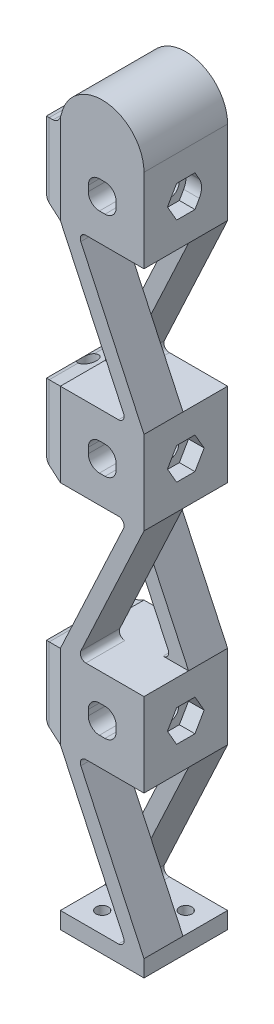
SolidWorks part; units mm, degrees
note: The reader was unsure of these and kept them because the rebuilt part matched: shared geometry of "Sketch1<3>", "Sketch1<4>", "Sketch1<5>".
material "PET"
ref_plane "Front Plane" through (0, 0, 0) normal (0, 0, 1) x (1, 0, 0)
ref_plane "Top Plane" through (0, 0, 0) normal (0, 1, 0) x (1, 0, 0)
ref_plane "Right Plane" through (0, 0, 0) normal (1, 0, 0) x (0, 0, -1)
sketch "Sketch1" plane through (0, 0, 0) normal (0, 0, 1) x (1, 0, 0)
  line L0 (0, 0) -> (57.9688, 0) construction
  line L1 (7.5, 12.867) -> (-7.5, 12.867)
  line L2 (7.5, -27.867) -> (-7.5, -27.867)
  line L3 (7.5, -27.867) -> (7.5, -12.867)
  line L4 (7.5, -12.867) -> (-7.5, -12.867)
  line L5 (-7.5, -27.867) -> (-7.5, -12.867)
  line L6 (7.5, -27.867) -> (-7.5, -12.867) construction
  line L7 (7.5, -12.867) -> (-7.5, -27.867) construction
  line L8 (-7.5, 27.867) -> (-7.5, 12.867)
  line L9 (0, 0) -> (0, 41.5625) construction
  line L10 (7.5, 27.867) -> (-7.5, 27.867)
  line L11 (7.5, 27.867) -> (7.5, 12.867)
  line L12 (-7.5, 12.867) -> (4.5, -12.867)
  line L13 (4.5, -12.867) -> (7.5, -12.867)
  line L14 (7.5, -12.867) -> (-4.5, 12.867)
  line L15 (-4.5, 12.867) -> (-7.5, 12.867)
  line L16 (7.5, 12.867) -> (-4.5, -12.867)
  line L17 (-7.5, -12.867) -> (4.5, 12.867)
  point P1 (0, -20.367)
  dimension "D1" = 15
  dimension "D2" = 65
  dimension "D3" = 3
extrude "Boss-Extrude1" add sketch "Sketch1" along normal mid plane 15 contours L5 L2 L3 L4
extrude "cross_flexure" add sketch "Sketch1<3>" against normal blind 7 from surface at 7.5 contours L17 L4 L16 L12 | L17 L14 L16 L1 | L17 L12 L16 L14 starting at face at (0, -20.367, 7.5)
sketch "Sketch1<3>" plane through (0, 0, 0) normal (0, 0, 1) x (1, 0, 0) same geometry as "Sketch1"
extrude "Boss-Extrude3" add sketch "Sketch1<4>" along normal blind 7 from surface at -7.5 contours L12 L17 L14 L1 | L14 L16 L12 L4 | L17 L12 L16 L14 starting at face at (0, -20.367, -7.5)
sketch "Sketch1<4>" plane through (0, 0, 0) normal (0, 0, 1) x (1, 0, 0) same geometry as "Sketch1"
extrude "Boss-Extrude4" add sketch "Sketch1<5>" along normal mid plane 15 contours L11 L10 L8 L1
sketch "Sketch1<5>" plane through (0, 0, 0) normal (0, 0, 1) x (1, 0, 0) same geometry as "Sketch1"
ref_plane "Plane1" through (0, 20.367, 0) normal (0, -1, 0) x (-1, 0, 0)
ref_plane "Plane2" through (7.5, -27.867, 7.5) normal (-1, 0, 0) x (0, 0, 1)
ref_plane "Plane3" through (0, -20.367, 0) normal (0, 1, 0) x (1, 0, 0)
mirror "Mirror2" about plane through (0, 20.367, 0) normal (0, -1, 0) of "cross_flexure", "Boss-Extrude3"
mirror "Mirror3" about plane through (0, 20.367, 0) normal (0, -1, 0) of "Boss-Extrude1"
mirror "Mirror4" about plane through (0, -20.367, 0) normal (0, 1, 0) of "cross_flexure"
mirror "Mirror5" about plane through (0, -20.367, 0) normal (0, 1, 0) of "Boss-Extrude3"
mirror "Mirror6" about plane through (0, -20.367, 0) normal (0, 1, 0) of "Boss-Extrude4"
sketch "Sketch29" plane through (0, 0, 7.5) normal (0, 0, 1) x (1, 0, 0)
  line L0 (7.5, 68.6011) -> (-7.5, 68.6011) construction
  line L1 (7.5, 68.6011) -> (-7.5, 68.6011)
  arc A0 (-7.5, 68.6011) -> (7.5, 68.6011) centre (0, 68.6011) cw
  line M10 (7.5, 68.6011) -> (-7.5, 68.6011)
extrude "Boss-Extrude5" add sketch "Sketch29" against normal up to surface (15 mm away) contours A0 M10 up to face at (0, 0, -7.5)
ref_plane "Plane4" through (0, -56.6011, 0) normal (0, 1, 0) x (1, 0, 0)
sketch "Sketch36" plane through (0, -56.6011, 0) normal (0, 1, 0) x (1, 0, 0)
  line L4 (7.5, -7.5) -> (7.5, 7.5)
  line L5 (7.5, 7.5) -> (-7.5, 7.5)
  line L6 (-7.5, 7.5) -> (-7.5, -7.5)
  line L7 (-7.5, -7.5) -> (7.5, -7.5)
  line L8 (7.5, -7.5) -> (7.5, 7.5)
  line L9 (7.5, 7.5) -> (-7.5, 7.5)
  line L10 (-7.5, 7.5) -> (-7.5, -7.5)
  line L11 (-7.5, -7.5) -> (7.5, -7.5)
  dimension "D1" = 0
extrude "Cut-Extrude1" cut sketch "Sketch36" against normal through all
fillet "Fillet1" radius 1 12 edges at (-4.5, -27.867, 4) (4.5, -53.6011, 4) (4.5, -27.867, -4) (-4.5, -53.6011, -4) (4.5, 12.867, 4) (-4.5, -12.867, 4) (4.5, -12.867, -4) (-4.5, 12.867, -4) (-4.5, 53.6011, 4) (4.5, 27.867, 4) (4.5, 53.6011, -4) (-4.5, 27.867, -4)
sketch "Sketch48" plane through (0, -53.6011, 0) normal (0, 1, 0) x (1, 0, 0)
  line L0 (0, 0) -> (-7.5, -7.5) construction
  line L1 (-7.5, -7.5) -> (7.5, -7.5) construction
  line L2 (0, 0) -> (-7.5, 7.5) construction
  line L3 (7.5, 7.5) -> (-7.5, 7.5) construction
  circle A0 centre (-3.75, -3.75) radius 1
  circle A1 centre (3.75, 3.75) radius 1
  point P6 (-3.75, -3.75)
  point P9 (3.75, 3.75)
  dimension "D1" = 2
hole_wizard "Ø2.2 (2.2) Diameter Hole1" positions "Sketch48" profile "Sketch49" hole size "Ø2.2" standard "DIN"
sketch "Sketch49" plane through (3.75, -53.6011, -3.75) normal (1, 0, 0) x (0, 0, 1)
  line L0 (0, 0) -> (0, 3)
  line L1 (0, 3) -> (1.1, 3)
  line L2 (1.1, 3) -> (1.1, 0)
  line L5 (1.1, 0) -> (0, 0)
  line L11 (0, -6.35) -> (0, 107.95) construction
  dimension "Thru Hole Dia." = 2.2
  dimension "Thru Hole Depth" = 3
ref_plane "Plane5" through (0, 0, 0) normal (0, 0, 1) x (1, 0, 0)
ref_plane "finger_surface" through (-12.5, 0, 0) normal (-1, 0, 0) x (0, 0, 1)
sketch "Sketch82" plane through (-12.5, 0, 0) normal (-1, 0, 0) x (0, 0, 1)
  line L0 (-6, 67.1011) -> (-6, 55.1011)
  line L1 (-6, 55.1011) -> (0.5, 55.1011)
  line L2 (0.5, 55.1011) -> (6, 55.1011)
  line L3 (6, 55.1011) -> (6, 67.1011)
  line L4 (6, 67.1011) -> (-6, 67.1011)
  line L5 (-7.5, 68.6011) -> (-7.5, 53.6011)
  line L6 (-7.5, 53.6011) -> (0.5, 53.6011)
  line L7 (0.5, 53.6011) -> (7.5, 53.6011)
  line L8 (7.5, 53.6011) -> (7.5, 68.6011)
  line L9 (7.5, 68.6011) -> (-7.5, 68.6011)
  line L10 (-7.5, 68.6011) -> (-7.5, 53.6011)
  line L11 (-7.5, 53.6011) -> (0.5, 53.6011)
  line L12 (0.5, 53.6011) -> (7.5, 53.6011)
  line L13 (7.5, 53.6011) -> (7.5, 68.6011)
  line L14 (7.5, 68.6011) -> (-7.5, 68.6011)
  dimension "D2" = 1.5
loft "Loft1" add section face at (-7.5, 59.6011, 0.1) section "Sketch82"
sketch "Sketch83" plane through (-12.5, 0, 0) normal (-1, 0, 0) x (0, 0, 1)
  line L0 (-6, 26.367) -> (-6, 14.367)
  line L1 (-6, 14.367) -> (-0.5, 14.367)
  line L2 (-0.5, 14.367) -> (6, 14.367)
  line L3 (6, 14.367) -> (6, 26.367)
  line L4 (6, 26.367) -> (-0.5, 26.367)
  line L5 (-0.5, 26.367) -> (-6, 26.367)
  line L6 (-7.5, 27.867) -> (-7.5, 12.867)
  line L7 (-7.5, 12.867) -> (-0.5, 12.867)
  line L8 (-0.5, 12.867) -> (7.5, 12.867)
  line L9 (7.5, 12.867) -> (7.5, 27.867)
  line L10 (7.5, 27.867) -> (-0.5, 27.867)
  line L11 (-0.5, 27.867) -> (-7.5, 27.867)
  line L12 (-7.5, 27.867) -> (-7.5, 12.867)
  line L13 (-7.5, 12.867) -> (-0.5, 12.867)
  line L14 (-0.5, 12.867) -> (7.5, 12.867)
  line L15 (7.5, 12.867) -> (7.5, 27.867)
  line L16 (7.5, 27.867) -> (-0.5, 27.867)
  line L17 (-0.5, 27.867) -> (-7.5, 27.867)
  line L18 (-7.5, -12.867) -> (-7.5, -27.867)
  line L19 (-7.5, -27.867) -> (0.5, -27.867)
  line L20 (0.5, -27.867) -> (7.5, -27.867)
  line L21 (7.5, -27.867) -> (7.5, -12.867)
  line L22 (7.5, -12.867) -> (0.5, -12.867)
  line L23 (0.5, -12.867) -> (-7.5, -12.867)
  line L24 (-7.5, -12.867) -> (-7.5, -27.867)
  line L25 (-7.5, -27.867) -> (0.5, -27.867)
  line L26 (0.5, -27.867) -> (7.5, -27.867)
  line L27 (7.5, -27.867) -> (7.5, -12.867)
  line L28 (7.5, -12.867) -> (0.5, -12.867)
  line L29 (0.5, -12.867) -> (-7.5, -12.867)
  line L30 (-6, -14.367) -> (-6, -26.367)
  line L31 (-6, -26.367) -> (0.5, -26.367)
  line L32 (0.5, -26.367) -> (6, -26.367)
  line L33 (6, -26.367) -> (6, -14.367)
  line L34 (6, -14.367) -> (0.5, -14.367)
  line L35 (0.5, -14.367) -> (-6, -14.367)
  dimension "D3" = 1.5
  dimension "D4" = 1.5
loft "Loft2" add section face at (-7.5, 20.367, -0.1667) section "Sketch83"
sketch "Sketch84" plane through (-12.5, 0, 0) normal (-1, 0, 0) x (0, 0, 1)
  line L0 (-6, -14.367) -> (-6, -26.367)
  line L1 (-6, -26.367) -> (0.5, -26.367)
  line L2 (0.5, -26.367) -> (6, -26.367)
  line L3 (6, -26.367) -> (6, -14.367)
  line L4 (6, -14.367) -> (0.5, -14.367)
  line L5 (0.5, -14.367) -> (-6, -14.367)
  line L6 (-7.5, -12.867) -> (-7.5, -27.867)
  line L7 (-7.5, -27.867) -> (0.5, -27.867)
  line L8 (0.5, -27.867) -> (7.5, -27.867)
  line L9 (7.5, -27.867) -> (7.5, -12.867)
  line L10 (7.5, -12.867) -> (0.5, -12.867)
  line L11 (0.5, -12.867) -> (-7.5, -12.867)
  line L12 (-7.5, -12.867) -> (-7.5, -27.867)
  line L13 (-7.5, -27.867) -> (0.5, -27.867)
  line L14 (0.5, -27.867) -> (7.5, -27.867)
  line L15 (7.5, -27.867) -> (7.5, -12.867)
  line L16 (7.5, -12.867) -> (0.5, -12.867)
  line L17 (0.5, -12.867) -> (-7.5, -12.867)
  dimension "D2" = 1.5
loft "Loft3" add section face at (-7.5, -20.367, 0.1667) section "Sketch84"
sketch "Sketch97" plane through (7.5, 0, 0) normal (1, 0, 0) x (0, 0, -1)
  line L0 (-7.5, 68.6011) -> (7.5, 53.6011) construction
  line L1 (7.5, 68.6011) -> (-7.5, 53.6011) construction
  line L2 (-7.5, 68.6011) -> (7.5, 68.6011) construction
  line L3 (-1.6454, 63.9511) -> (-3.2909, 61.1011)
  line L4 (-3.2909, 61.1011) -> (-1.6454, 58.2511)
  line L5 (-1.6454, 58.2511) -> (1.6454, 58.2511)
  line L6 (1.6454, 58.2511) -> (3.2909, 61.1011)
  line L7 (3.2909, 61.1011) -> (1.6454, 63.9511)
  line L8 (1.6454, 63.9511) -> (-1.6454, 63.9511)
  circle A0 centre (0, 61.1011) radius 2.85 construction
  point P8 (0, 61.1011)
  dimension "D1" = 5.7
extrude "hex_nut M3" cut sketch "Sketch97" against normal blind 2.8
sketch "Sketch98" plane through (4.7, 0, 0) normal (1, 0, 0) x (0, 0, -1)
  line L0 (-1.6454, 63.9511) -> (1.6454, 58.2511) construction
  line L1 (1.6454, 63.9511) -> (-1.6454, 58.2511) construction
  circle A0 centre (0, 61.1011) radius 1.6
  point P8 (0, 61.1011)
  dimension "D1" = 3.2
extrude "Cut-Extrude5" cut sketch "Sketch98" against normal blind 8
sketch "Sketch99" plane through (0, 0, 0) normal (0, 0, 1) x (1, 0, 0)
  line L0 (7.5, 68.6011) -> (7.5, 53.6011) construction
  line L1 (-12.5, 55.1011) -> (-12.5, 67.1011) construction
  line L2 (7.5, 68.6011) -> (7.5, 53.6011) construction
  line L3 (-12.5, 55.1011) -> (-12.5, 67.1011) construction
  line L4 (-7.5, -56.6011) -> (7.5, -56.6011) construction
  line L5 (-7.5, -56.6011) -> (7.5, -56.6011) construction
  line L6 (7.5, 61.1011) -> (-3, 61.1011)
  line L7 (-10, 54.1011) -> (-10, -56.6011)
  arc A0 (-3, 61.1011) -> (-10, 54.1011) centre (-3, 54.1011) ccw
  dimension "D2" = 7
  dimension "D1" = 5
sweep "tendon_path" cut path "Sketch99" circular profile diameter 3 parameters "D3"=3
fillet "Fillet6" radius 3 14 edges at (-7.5, 68.6011, 0) (6.1, 61.1011, -3.2909)
sketch "Sketch111" plane through (0, 0, 7.5) normal (0, 0, 1) x (1, 0, 0)
  line L0 (-7.5, -12.867) -> (7.5, -12.867)
  line L1 (-7.5, -12.867) -> (-7.5, -27.867)
  line L2 (-7.5, -27.867) -> (7.5, -27.867)
  line L3 (7.5, -23.742) -> (7.5, -31.992) construction
  line L4 (7.5, -27.867) -> (7.5, -12.867) construction
  line L5 (7.5, -27.867) -> (7.5, -12.867)
  line L6 (17.5, -37.867) -> (17.5, -2.867)
  line L7 (-17.5, -2.867) -> (17.5, -2.867)
  line L8 (-17.5, -2.867) -> (-17.5, -37.867)
  line L9 (-17.5, -37.867) -> (17.5, -37.867)
  line L10 (-2.5, -19.867) -> (-2.5, -20.867)
  line L11 (-0.5, -22.867) -> (0.5, -22.867)
  line L12 (2.5, -20.867) -> (2.5, -19.867)
  line L13 (-0.5, -17.867) -> (0.5, -17.867)
  line L14 (-2.5, -17.867) -> (-2.5, -22.867) construction
  line L15 (-2.5, -22.867) -> (2.5, -22.867) construction
  line L16 (2.5, -22.867) -> (2.5, -17.867) construction
  line L17 (-2.5, -17.867) -> (2.5, -17.867) construction
  arc A0 (-2.5, -20.867) -> (-0.5, -22.867) centre (-0.5, -20.867) ccw
  arc A1 (0.5, -22.867) -> (2.5, -20.867) centre (0.5, -20.867) ccw
  arc A2 (2.5, -19.867) -> (0.5, -17.867) centre (0.5, -19.867) ccw
  arc A3 (-2.5, -19.867) -> (-0.5, -17.867) centre (-0.5, -19.867) cw
  dimension "D3" = 2
  dimension "D1" = 10
  dimension "D2" = 5
extrude "Cut-Extrude6" cut sketch "Sketch111" against normal up to surface (15 mm away) contours A3 L10 A0 L11 A1 L12 A2 L13 up to face at (0.3131, 3.5351, -7.5)
pattern_linear "LPattern1" count 3 spacing 40.7341 along (0, 1, 0) of "Cut-Extrude6"
pattern_linear "hex_nuts_pattern" count 3 spacing 40.7341 along (0, -1, 0) of "hex_nut M3"
pattern_linear "LPattern3" count 3 spacing 40.7341 along (0, -1, 0) of "tendon_path"
equation "\"a\"=7"
equation "\"D1@cross_flexure\" = \"a\""
equation "\"D1@Boss-Extrude3\"= \"a\""
equation "\"d_sheath\"= 3.5'M2 threaded inserts"
equation "\"r\"= 7'radius for tendon routing"
equation "\"angle\" = 65deg'angle of cross flexures"
equation "\"side_length\"= 15mm"
equation "\"d\"= \"side_length\" + \"d1\"'for linear patterns"
equation "\"w\"= 3mm'width of the cross flexures"
equation "\"d1\"= tan ( \"angle\" ) * \"diff\"'dist between top face and bottom face of 2 consecutive fingers"
equation "\"diff\"= \"side_length\" - \"w\""
equation "\"D3@Sketch1\"=\"w\""
equation "\"D2@Sketch1\"=\"angle\""
equation "\"offset\"= 1.5'loft offset for finger surface"
equation "\"D2@Sketch82\"=\"offset\""
equation "\"D3@Sketch83\"=\"offset\""
equation "\"D4@Sketch83\"=\"offset\""
equation "\"D2@Sketch84\"=\"offset\""
equation "\"D3@LPattern1\"=\"d\""
equation "\"D2@Sketch99\"=\"r\""
equation "\"D3@hex_nuts_pattern\"=\"d\""
equation "\"D3@LPattern3\"=\"d\""
equation "\"finger_thickness\"= 15mm"
equation "\"D1@Boss-Extrude4\"=\"finger_thickness\""
equation "\"D1@Boss-Extrude1\"=\"finger_thickness\""
